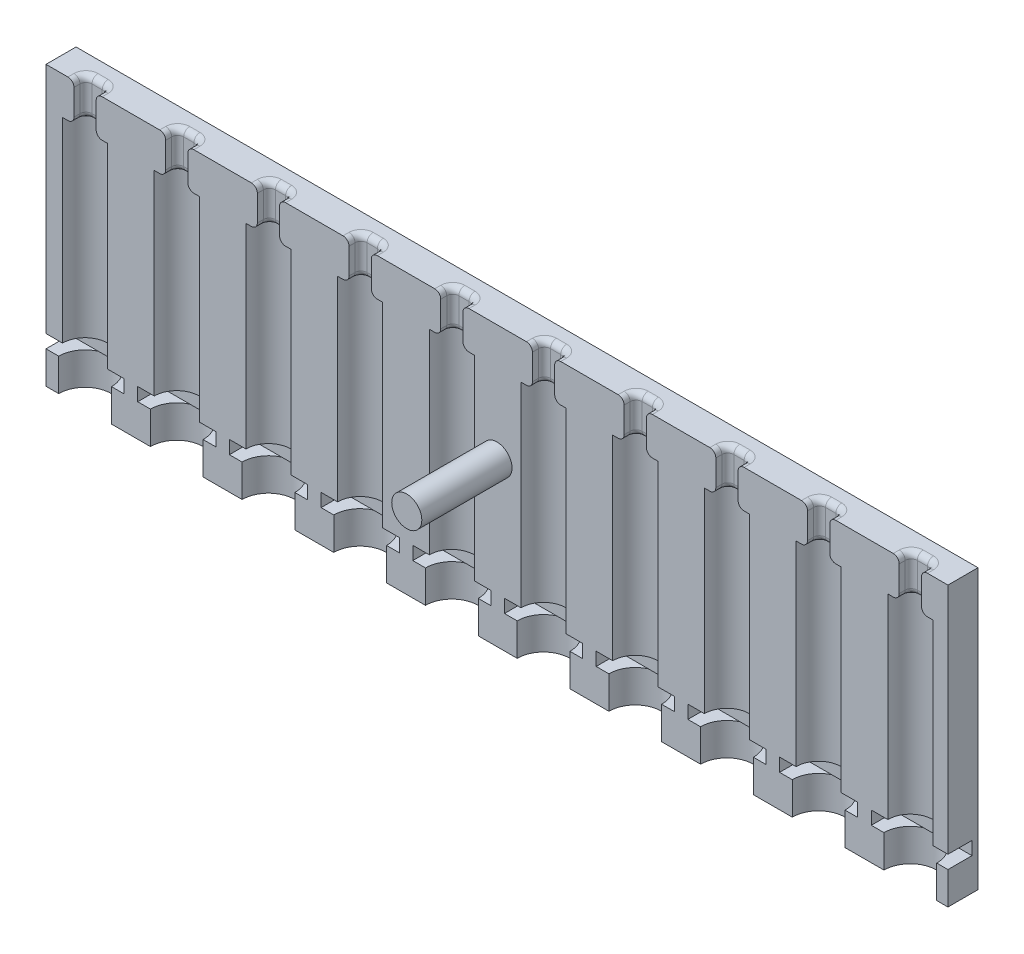
SolidWorks part; units mm, degrees
ref_plane "Front Plane" through (0, 0, 0) normal (1, 0, 0) x (0, 1, 0)
ref_plane "Top Plane" through (0, 0, 0) normal (0, 0, 1) x (0, 1, 0)
ref_plane "Right Plane" through (0, 0, 0) normal (0, 1, 0) x (-1, 0, 0)
sketch "Sketch1" plane through (0, 0, 0) normal (0, 0, 1) x (0, 1, 0)
  line L1 (-75, -150) -> (75, -150)
  line L2 (-75, -150) -> (-75, 150)
  line L3 (-75, 150) -> (75, 150)
  line L4 (75, -150) -> (75, 150)
  line L5 (-75, -150) -> (75, 150) construction
  line L6 (-75, 150) -> (75, -150) construction
  point P0 (0, 0)
  dimension "D1" = 300
  dimension "D2" = 150
extrude "Boss-Extrude1" add sketch "Sketch1" along normal blind 10
sketch "flange slit" plane through (0, 0, 10) normal (0, 0, 1) x (1, 0, 0)
  line L0 (0, 75) -> (0, -75) construction
  line L1 (150, 75) -> (-150, 75) construction
  line L2 (-150, -75) -> (150, -75) construction
  line L3 (-124, 0) -> (150, 0) construction
  line L5 (150, -75) -> (150, 75) construction
  line L6 (-70.7884, -63.1) -> (-70.7884, -60.9) construction
  line L7 (-150, 75) -> (-124, 75) construction
  line L9 (-150, -75) -> (-124, -75) construction
  line L11 (-70.7884, -63.1) -> (-70.7884, -62) construction
  line L12 (-150, -59.8) -> (-124, -59.8)
  line L13 (-150, -59.8) -> (-150, -64.2)
  line L14 (-150, -64.2) -> (-124, -64.2)
  line L19 (-124, -59.8) -> (-124, -64.2)
  line L20 (-150, -59.8) -> (-124, -64.2) construction
  line L21 (-150, -64.2) -> (-124, -59.8) construction
  line L26 (-70.7884, -62) -> (-150, -62) construction
  point P8 (-137, -62)
  point P23 (0, 0)
  dimension "D1" = 26
  dimension "D2" = 2.2
extrude "Flange Slot" cut sketch "flange slit" against normal blind 8
sketch "Sketch3" plane through (0, 0, 10) normal (0, 0, 1) x (1, 0, 0)
  line L0 (-150, -75) -> (150, -75) construction
  line L1 (-150, 75) -> (-124, 75) construction
  line L2 (-150, 75) -> (-150, -75) construction
  line L3 (-150, -75) -> (-124, -75) construction
  line L4 (-124, 75) -> (-124, -75) construction
  line L5 (-150, 75) -> (-124, -75) construction
  line L6 (-150, -75) -> (-124, 75) construction
  line L7 (-124, -64.2) -> (-124, -59.8) construction
  line L8 (-124, -59.8) -> (-150, -59.8) construction
  line L9 (-144.5, -59.8) -> (-129.5, -59.8)
  line L10 (-144.5, -59.8) -> (-144.5, 5.2)
  line L11 (-144.5, 5.2) -> (-129.5, 5.2)
  line L12 (-129.5, -59.8) -> (-129.5, 5.2)
  line L13 (-144.5, -59.8) -> (-129.5, 5.2) construction
  line L14 (-144.5, 5.2) -> (-129.5, -59.8) construction
  line L15 (-137, 75) -> (-137, -59.8) construction
  line L16 (-137, 5.2) -> (-137, -59.8)
  line L18 (-144.5, 5.2) -> (-137, 5.2)
  line L19 (-144.5, 5.2) -> (-144.5, -59.8)
  line L20 (-144.5, -59.8) -> (-137, -59.8)
  line L21 (-137, 5.2) -> (-137, -59.8)
  line L22 (-144.5, 5.2) -> (-137, -59.8) construction
  line L23 (-144.5, -59.8) -> (-137, 5.2) construction
  point P4 (-137, 0)
  point P14 (-137, -27.3)
  point P23 (-140.75, -27.3)
  dimension "D1" = 65
  dimension "D2" = 15
revolve "Syringe Body Slot" cut sketch "Sketch3" angle 360 about L15 region at (-140.75, -27.3, 10)
sketch "Sketch6" plane through (0, 0, 10) normal (0, 0, 1) x (0, -1, 0)
  line L0 (75, 150) -> (-75, 150) construction
  line L1 (-75, -150) -> (-17.7492, -150)
  line L2 (-75, -150) -> (-75, 150)
  line L3 (-75, 150) -> (-17.7492, 150)
  line L4 (-17.7492, -150) -> (-17.7492, 150)
  line L5 (-75, -150) -> (-17.7492, 150) construction
  line L6 (-75, 150) -> (-17.7492, -150) construction
  point P4 (-46.3746, 0)
extrude "Cut-Extrude2" cut sketch "Sketch6" against normal through all
sketch "Sketch7" plane through (0, 0, 10) normal (0, 0, 1) x (1, 0, 0)
  line L0 (-150, -64.2) -> (-124, -64.2) construction
  line L1 (-137, -64.2) -> (-145.7782, -64.2)
  line L2 (-137, -64.2) -> (-137, -75)
  line L3 (-137, -75) -> (-145.7782, -75)
  line L4 (-145.7782, -64.2) -> (-145.7782, -75)
  line L5 (-137, -64.2) -> (-145.7782, -75) construction
  line L6 (-137, -75) -> (-145.7782, -64.2) construction
  line L7 (-150, -75) -> (150, -75) construction
  point P4 (-141.3891, -69.6)
revolve "Plunger Slot" cut sketch "Sketch7" angle 360 about L2
sketch "Sketch8" plane through (0, 0, 10) normal (0, 0, 1) x (1, 0, 0)
  line L0 (-144.5, 5.2) -> (-129.5, 5.2) construction
  line L1 (-140.7, -7.3492) -> (-133.3, -7.3492)
  line L2 (-140.7, -7.3492) -> (-140.7, 17.7492)
  line L3 (-140.7, 17.7492) -> (-133.3, 17.7492)
  line L4 (-133.3, -7.3492) -> (-133.3, 17.7492)
  line L5 (-140.7, -7.3492) -> (-133.3, 17.7492) construction
  line L6 (-140.7, 17.7492) -> (-133.3, -7.3492) construction
  line L7 (-150, 17.7492) -> (150, 17.7492) construction
  point P0 (-137, 5.2)
  dimension "D1" = 7.4
extrude "Needle Slot" cut sketch "Sketch8" against normal blind 4
fillet "Fillet1" radius 2 8 edges at (-140.7, 17.7492, 8) (-140.7, 5.2, 8) (-133.3, 17.7492, 8) (-133.3, 5.2, 8) (-140.7, 11.4746, 6) (-137, 17.7492, 6) (-133.3, 11.4746, 6) (-137, 5.2, 6)
pattern_linear "LPattern3" count 10 spacing 30.5 along (1, 0, 0) of "Plunger Slot", "Syringe Body Slot", "Flange Slot", "Needle Slot", "Fillet1"
sketch "Sketch9" plane through (0, 0, 10) normal (0, 0, 1) x (1, 0, 0)
  circle A0 centre (0, -21.0254) radius 5
  dimension "D1" = 10
extrude "Boss-Extrude3" add sketch "Sketch9" along normal blind 30
